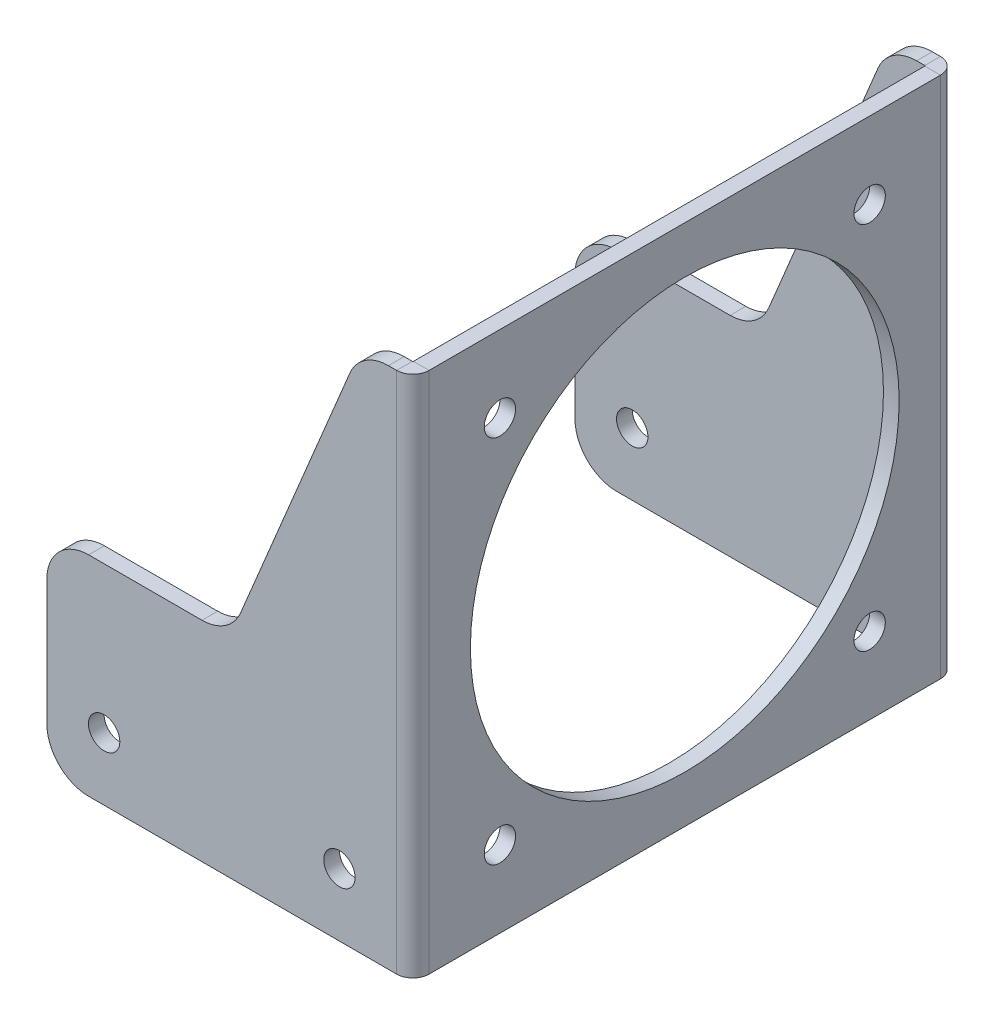
SolidWorks part; units mm, degrees
note: The reader was unsure of these and kept them because the rebuilt part matched: flange length of "边线-法兰1".
ref_plane "前视基准面" through (0, 0, 0) normal (0, 0, 1) x (1, 0, 0)
ref_plane "上视基准面" through (0, 0, 0) normal (0, 1, 0) x (1, 0, 0)
ref_plane "右视基准面" through (0, 0, 0) normal (1, 0, 0) x (0, 0, -1)
sketch "草图1" plane through (0, 0, 0) normal (1, 0, 0) x (0, 0, -1)
  line L12 (-49, -50) -> (49, -50)
  line L13 (-49, -50) -> (-49, 50)
  line L14 (-49, 50) -> (49, 50)
  line L15 (49, -50) -> (49, 50)
  line L16 (-49, -50) -> (49, 50) construction
  line L17 (-49, 50) -> (49, -50) construction
  line L18 (-35.3553, -35.3553) -> (35.3553, -35.3553) construction
  line L19 (-35.3553, -35.3553) -> (-35.3553, 35.3553) construction
  line L20 (-35.3553, 35.3553) -> (35.3553, 35.3553) construction
  line L21 (35.3553, -35.3553) -> (35.3553, 35.3553) construction
  line L22 (-35.3553, -35.3553) -> (35.3553, 35.3553) construction
  line L23 (-35.3553, 35.3553) -> (35.3553, -35.3553) construction
  circle A0 centre (0, 0) radius 41
  circle A1 centre (-35.3553, 35.3553) radius 3
  circle A2 centre (35.3553, 35.3553) radius 3
  circle A3 centre (35.3553, -35.3553) radius 3
  circle A4 centre (-35.3553, -35.3553) radius 3
  point P0 (0, 0)
  dimension "D1" = 6
  dimension "D4" = 82
  dimension "D2" = 98
  dimension "D3" = 100
  dimension "D5" = 100
base flange "基体-法兰1" sketch "草图1" thickness 3 reverse thickness direction no parameters "D1"=0.1
edge flange "边线-法兰1" sketch "草图6" flange profiles "草图6", "草图7" flange angle 90 flange length 70 flange position material outside bend radius 0.1 thickness 3 relief rectangular parameters "D6"=10, "D8"=1
sketch "草图6" plane through (-3, 0, 49) normal (0, 0, 1) x (0, 1, 0)
  line L0 (50, 0) -> (-50, 0) construction
  line L1 (50, 0) -> (-50, 0)
  line L2 (-50, 0) -> (-50, 67)
  line L3 (-50, 67) -> (50, 67)
  line L4 (50, 67) -> (50, 0)
sketch "草图7" plane through (-3, 0, -49) normal (0, 0, -1) x (0, -1, 0)
  line L0 (50, 0) -> (-50, 0) construction
  line L1 (50, 0) -> (-50, 0)
  line L2 (-50, 0) -> (-50, 67)
  line L3 (-50, 67) -> (50, 67)
  line L4 (50, 67) -> (50, 0)
bend "边线折弯1" bend radius 0.1 bend angle 90 parameters "D5"=1
bend "边线折弯2" bend radius 0.1 bend angle 90 parameters "D5"=2
sketch "草图8" plane through (0, 0, 52) normal (0, 0, 1) x (1, 0, 0)
  line L0 (-10, 50) -> (-70, 50)
  line L1 (-3.1, 50) -> (-70, 50) construction
  line L2 (-70, 50) -> (-70, -10)
  line L3 (-70, 50) -> (-70, -50) construction
  line L4 (-70, -10) -> (-35, -10)
  line L5 (-35, -10) -> (-10, 50)
  line L6 (-59.05, -38) -> (-14.05, -38) construction
  line L7 (-70, -50) -> (-3.1, -50) construction
  line L8 (0, 50) -> (0, -50) construction
  circle A0 centre (-14.05, -38) radius 3
  circle A1 centre (-59.05, -38) radius 3
  point P13 (-36.55, -38)
  point P16 (-36.55, -50)
  point P17 (-70, -15.6571)
  point P18 (-9.6196, 50)
  point P19 (-38.0747, -18.9246)
  dimension "D1" = 6
  dimension "D2" = 45
  dimension "D3" = 12
  dimension "D4" = 60
  dimension "D5" = 10
  dimension "D6" = 35
extrude "切除-拉伸1" cut sketch "草图8" against normal through all normal cut yes
fillet "圆角1" radius 8 8 edges at (-70, -50, 50.5) (-70, -50, -50.5) (-70, -10, 50.5) (-35, -10, 50.5) (-35, -10, -50.5) (-10, 50, 50.5) (-10, 50, -50.5) (-70, -10, -50.5)
sketch "折弯-线1" plane through (0, 0, 0) normal (0, 1, 0) x (1, 0, 0)
sketch "边界框1" plane through (0, 0, 0) normal (0, 1, 0) x (1, 0, 0)
sheet metal parameters "钣金9" thickness 3 parameters "D1"=0.1
flat pattern "平板型式9" [suppressed]
sketch "折弯-线2" plane through (0, 0, 0) normal (0, 1, 0) x (1, 0, 0)
sketch "边界框2" [suppressed] plane through (0, 0, 0) normal (0, 1, 0) x (1, 0, 0)
sheet metal parameters "钣金10" thickness 3 parameters "D1"=0.1
flat pattern "平板型式9" [suppressed]
sketch "折弯-线2" plane through (0, 0, 0) normal (0, 1, 0) x (1, 0, 0)
sketch "边界框2" [suppressed] plane through (0, 0, 0) normal (0, 1, 0) x (1, 0, 0)
bend of the flat pattern "展平-<边线折弯1>1"
bend of the flat pattern "展平-<边线折弯2>1"
sheet metal parameters "钣金11" thickness 3 parameters "D1"=0.1
flat pattern "平板型式9" [suppressed]
sketch "折弯-线2" plane through (0, 0, 0) normal (0, 1, 0) x (1, 0, 0)
sketch "边界框2" [suppressed] plane through (0, 0, 0) normal (0, 1, 0) x (1, 0, 0)
bend of the flat pattern "展平-<边线折弯1>1"
bend of the flat pattern "展平-<边线折弯2>1"
